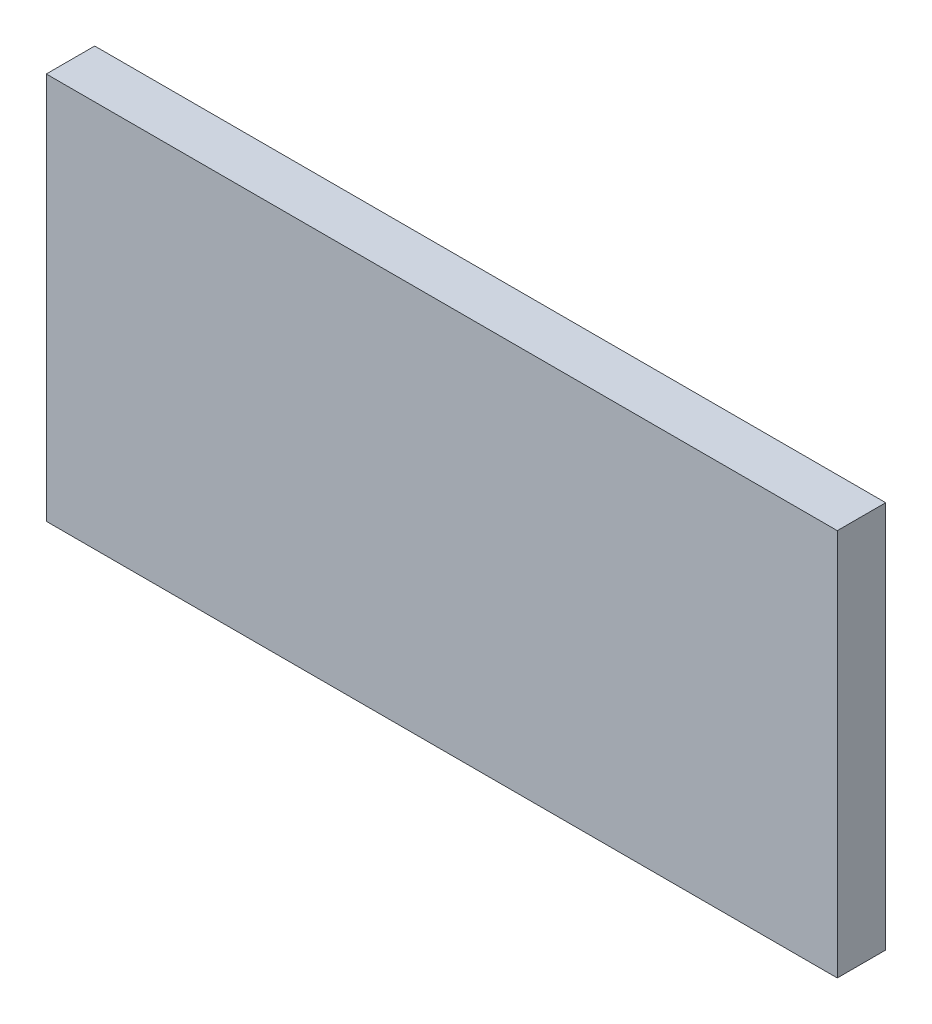
SolidWorks part; units mm, degrees
ref_plane "Front Plane" through (0, 0, 0) normal (0, 0, 1) x (1, 0, 0)
ref_plane "Top Plane" through (0, 0, 0) normal (0, 1, 0) x (1, 0, 0)
ref_plane "Right Plane" through (0, 0, 0) normal (1, 0, 0) x (0, 0, -1)
sketch "Sketch1" plane through (0, 0, 0) normal (0, 0, 1) x (1, 0, 0)
  line L1 (98, -48) -> (-98, -48)
  line L2 (98, -48) -> (98, 48)
  line L3 (98, 48) -> (-98, 48)
  line L4 (-98, -48) -> (-98, 48)
  line L5 (98, -48) -> (-98, 48) construction
  line L6 (98, 48) -> (-98, -48) construction
  point P0 (0, 0)
  dimension "D1" = 96
  dimension "D2" = 196
extrude "Extrude1" add sketch "Sketch1" against normal blind 12
